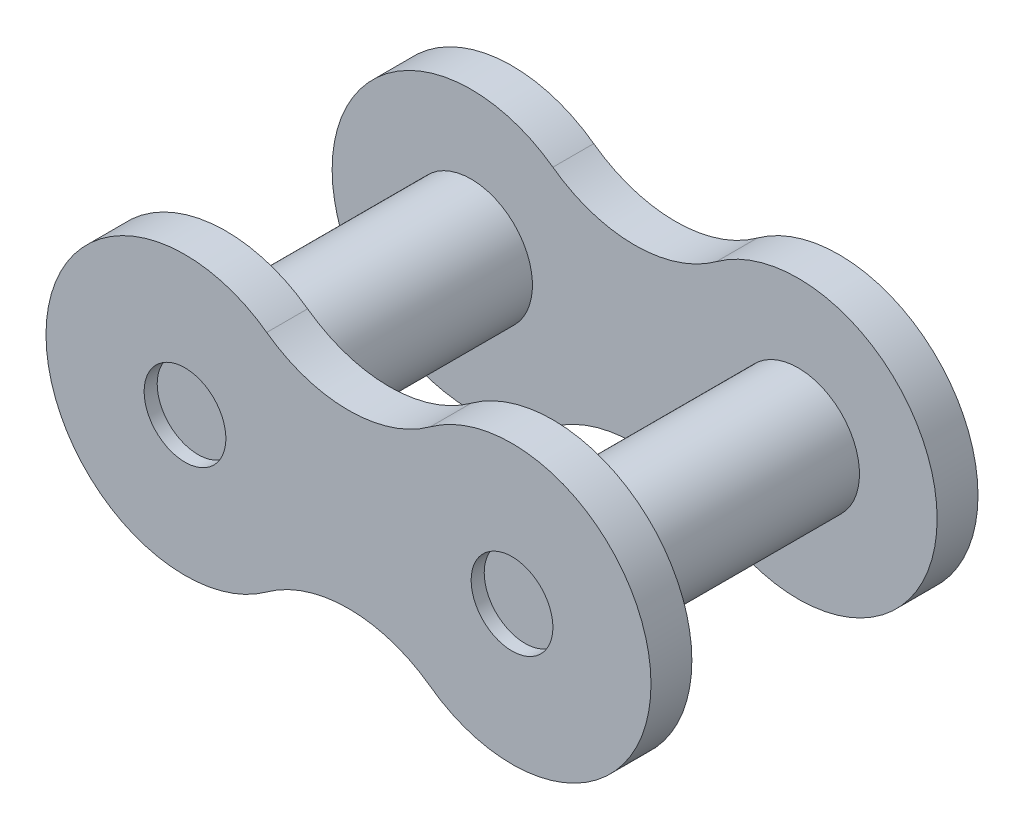
SolidWorks part; units mm, degrees
ref_plane "Front Plane" through (0, 0, 0) normal (0, 0, 1) x (1, 0, 0)
ref_plane "Top Plane" through (0, 0, 0) normal (0, 1, 0) x (1, 0, 0)
ref_plane "Right Plane" through (0, 0, 0) normal (1, 0, 0) x (0, 0, -1)
sketch "Sketch2" plane through (0, 0, 0) normal (0, 0, 1) x (1, 0, 0)
  circle A0 centre (0, 0) radius 2.3813
  circle A1 centre (6.35, 0) radius 2.3813
  arc A2 (1.5875, 1.7749) -> (4.7625, 1.7749) centre (3.175, 3.5498) ccw
  arc A3 (1.5875, -1.7749) -> (4.7625, -1.7749) centre (3.175, -3.5498) cw
  circle A4 centre (0, 0) radius 1.1906
  circle A5 centre (6.35, 0) radius 1.1906
  dimension "D2" = 4.7625
  dimension "D3" = 2.3813
  dimension "D1" = 6.35
extrude "Boss-Extrude1" add sketch "Sketch2" along normal blind 0.7937 contours A0 A4 | A0 A3 A1 A2 | A1 A5 region at (2.1123, -0.9446, 0) region at (3.175, 0, 0) region at (7.2946, 2.1123, 0)
sketch "Sketch3" plane through (0, 0, 0) normal (0, 0, -1) x (-1, 0, 0)
  circle A0 centre (-6.35, 0) radius 2.6988
  arc A1 (-4.7625, 1.7749) -> (-4.7625, -1.7749) centre (-6.35, 0) ccw construction
  circle A2 centre (-12.7, 0) radius 2.6987
  arc A3 (-11.1125, 2.1825) -> (-7.9375, 2.1825) centre (-9.525, 4.3649) ccw
  arc A4 (-11.1125, -2.1825) -> (-7.9375, -2.1825) centre (-9.525, -4.3649) cw
  circle A5 centre (-6.35, 0) radius 1.1906 construction
  circle A6 centre (-6.35, 0) radius 1.1906
  circle A7 centre (-12.7, 0) radius 1.1906
  arc M5 (-1.5875, 1.7749) -> (-4.7625, 1.7749) centre (-3.175, 3.5498) cw
  arc M6 (-4.7625, 1.7749) -> (-4.7625, -1.7749) centre (-6.35, 0) ccw
  arc M7 (-4.7625, -1.7749) -> (-1.5875, -1.7749) centre (-3.175, -3.5498) cw
  circle M8 centre (-6.35, 0) radius 1.1906
  dimension "D1" = 0.3175
  dimension "D2" = 6.35
extrude "Boss-Extrude2" add sketch "Sketch3" along normal blind 0.7937 separate body contours A2 A7 | A0 M7 M5 M6 M8 | A0 M5 M7 M6 | A2 A4 A0 A3 region at (5.7852, 2.5633, 0) region at (9.525, 0, 0) region at (3.8053, 0.6609, 0) region at (10.3631, 1.1899, 0)
extrude "Boss-Extrude3" add sketch "Sketch3<4>" against normal blind 3.175 from surface contours M8 | A7 region at (6.35, 0, 0) region at (12.7, 0, 0) starting at face at (9.525, 0, -0.7937)
sketch "Sketch3<4>" plane through (0, 0, 0) normal (0, 0, -1) x (-1, 0, 0) same geometry as "Sketch3"
mirror "Mirror1" about plane through (6.35, 0, 2.3812) normal (0, 0, -1) of bodies 105 101
combine bodies "Combine1" operation type add bodies to combine 105 106
delete or keep bodies "Body-Delete/Keep 1" type delete bodies bodies 101 107
ref_plane "Plane1" through (0, 0, 2.3812) normal (0, 0, 1) x (1, 0, 0)
sketch "Sketch4" plane through (0, 0, -0.7937) normal (0, 0, -1) x (-1, 0, 0)
  circle A9 centre (-6.35, 0) radius 0.7938
  circle A10 centre (-12.7, 0) radius 0.7937
  arc A11 (-11.1125, 2.1825) -> (-11.1125, -2.1825) centre (-12.7, 0) ccw construction
  arc A12 (-7.9375, -2.1825) -> (-7.9375, 2.1825) centre (-6.35, 0) ccw construction
  point P2 (0, 0)
  dimension "D1" = 1.5875
extrude "Cut-Extrude1" cut sketch "Sketch4" against normal blind 0.254
mirror "Mirror2" about plane through (0, 0, 2.3812) normal (0, 0, 1) of "Cut-Extrude1"
